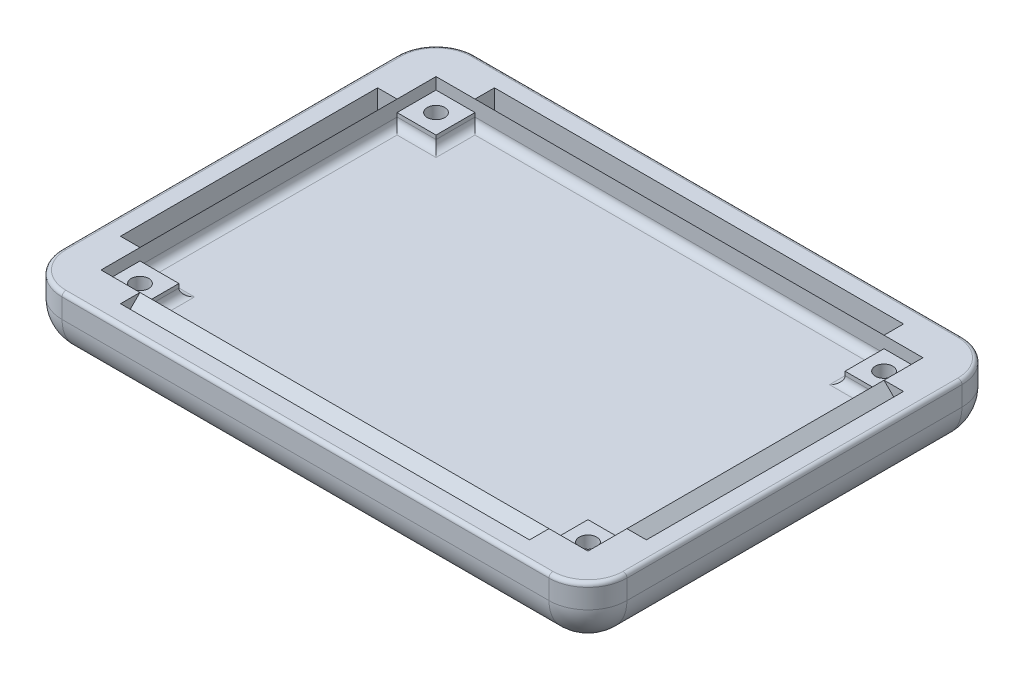
SolidWorks part; units mm, degrees
ref_plane "Front Plane" through (0, 0, 0) normal (0, 0, 1) x (1, 0, 0)
ref_plane "Top Plane" through (0, 0, 0) normal (0, 1, 0) x (1, 0, 0)
ref_plane "Right Plane" through (0, 0, 0) normal (1, 0, 0) x (0, 0, -1)
sketch "Sketch1" plane through (0, 0, 0) normal (0, 1, 0) x (1, 0, 0)
  line L0 (62.5, -43) -> (62.5, 43)
  line L1 (72.5, -53) -> (-72.5, -53)
  line L2 (72.5, -53) -> (72.5, 53)
  line L3 (72.5, 53) -> (-72.5, 53)
  line L4 (-72.5, -53) -> (-72.5, 53)
  line L5 (0, 53) -> (0, -53) construction
  line L6 (72.5, 0) -> (-72.5, 0) construction
  line L7 (62.5, 43) -> (-62.5, 43)
  line L8 (-62.5, -43) -> (-62.5, 43)
  line L9 (62.5, -43) -> (-62.5, -43)
  point P0 (0, 0)
  point P12 (0, 0)
  point P13 (0, 0)
  dimension "D1" = 145
  dimension "D2" = 106
  dimension "D3" = 10
extrude "Boss-Extrude1" add sketch "Sketch1" along normal blind 16 contours L9 L0 L7 L8 | L0 L9 L8 L7 | L4 L1 L2 L3 region at (0, 0, 0) region at (0, 0, 51.2039)
extrude "Cut-Extrude1" cut sketch "Sketch1<4>" against normal offset from surface (6 mm away) 10 from surface contours L8 L7 L0 L9 up to face at (0, 0, 0) starting at face at (0, 16, 0)
sketch "Sketch1<4>" plane through (0, 0, 0) normal (0, 1, 0) x (1, 0, 0) same geometry as "Sketch1"
sketch "Sketch3" plane through (0, 0, 0) normal (1, 0, 0) x (0, 0, -1)
  line L0 (-53, 16) -> (53, 16) construction
  line L2 (-48, 16) -> (-43, 16)
  line L3 (-53, 16) -> (-53, 0) construction
  line L4 (-48, 16) -> (-48, 11)
  line L5 (-48, 11) -> (-43, 16)
  point P6 (-46.4757, 16)
  point P7 (0, 0)
  dimension "D1" = 5
  dimension "D2" = 5
extrude "Cut-Extrude3" cut sketch "Sketch3" against normal offset from surface 10 and the other way offset from surface 10 up to face at (-62.5, 13, 0) other way up to face at (62.5, 13, 0)
sketch "Sketch4" plane through (0, 0, 0) normal (0, 0, 1) x (1, 0, 0)
  line L0 (72.5, 16) -> (-72.5, 16) construction
  line L1 (-62.5, 16) -> (-67.5, 16)
  line L2 (-67.5, 16) -> (-67.5, 11)
  line L3 (-67.5, 11) -> (-62.5, 16)
  line L4 (-72.5, 16) -> (-72.5, 0) construction
  dimension "D1" = 5
  dimension "D2" = 5
extrude "Cut-Extrude4" cut sketch "Sketch4" against normal offset from surface 10 and the other way offset from surface 10 up to face at (0, 13, -43) other way up to face at (0, 14, 43)
mirror "Mirror1" about plane through (0, 0, 0) normal (1, 0, 0) of "Cut-Extrude4"
mirror "Mirror4" about plane through (0, 0, 0) normal (0, 0, 1) of "Cut-Extrude3"
fillet "Fillet1" radius 10 8 edges at (0, 0, 53) (72.5, 0, 0) (0, 0, -53) (-72.5, 0, 0) (-72.5, 8, -53) (72.5, 8, -53) (72.5, 8, 53) (-72.5, 8, 53)
sketch "Sketch5" plane through (0, 10, 0) normal (0, 1, 0) x (1, 0, 0)
  line L2 (-62.5, 33) -> (-67.5, 33) construction
  line L3 (-52.5, 33) -> (-62.5, 33)
  line L4 (-62.5, -43) -> (62.5, -43)
  line L5 (62.5, -43) -> (62.5, 43)
  line L6 (62.5, 43) -> (-62.5, 43)
  line L7 (-62.5, 43) -> (-62.5, -43)
  line L8 (-62.5, -43) -> (62.5, -43)
  line L9 (62.5, -43) -> (62.5, 43)
  line L12 (-52.5, 33) -> (-52.5, 43)
  line L13 (-52.5, 43) -> (-62.5, 43)
  line L14 (-62.5, 33) -> (-62.5, 43)
  line L15 (-57.5, 43) -> (-57.5, 33) construction
  line L16 (-52.5, 38) -> (-62.5, 38) construction
  line L17 (-52.5, 43) -> (-52.5, 48) construction
  line L18 (-62.5, 43) -> (-62.5, 33) construction
  point P2 (-57.5, 38)
  point P15 (0, 0)
  line M7 (62.5, 43) -> (-62.5, 43)
  line M8 (-62.5, 43) -> (-62.5, -43)
  dimension "D1" = 0
extrude "Boss-Extrude3" add sketch "Sketch5" along normal blind 3 contours L3 L12 M7 M8 region at (-57.5, 10, -38)
hole_wizard "M4 Clearance Hole1" positions "Sketch6" profile "Sketch7" hole size "M4" standard "ANSI Metric"
sketch "Sketch6" plane through (0, 13, 0) normal (0, 1, 0) x (1, 0, 0)
  point P0 (-57.5, 38)
sketch "Sketch7" plane through (-57.5, 13, -38) normal (1, 0, 0) x (0, 0, 1)
  line L0 (0, 0) -> (0, 7.25)
  line L1 (0, 7.25) -> (2.25, 5)
  line L2 (2.25, 5) -> (2.25, 0)
  line L5 (2.25, 0) -> (0, 0)
  line L10 (0, 7.25) -> (-2.25, 5) construction
  line L11 (0, -6.35) -> (0, 107.95) construction
  dimension "Hole Dia." = 4.5
  dimension "Hole Depth" = 5
  dimension "Drill Angle" = 90
mirror "Mirror5" about plane through (0, 0, 0) normal (0, 0, 1) of "M4 Clearance Hole1", "Boss-Extrude3"
mirror "Mirror6" about plane through (0, 0, 0) normal (1, 0, 0) of "Mirror5", "M4 Clearance Hole1", "Boss-Extrude3"
fillet "Fillet3" radius 2 12 edges at (52.5, 10, 38) (0, 10, 43) (-52.5, 10, 38) (-57.5, 10, 33) (-62.5, 10, 0) (-57.5, 10, -33) (-52.5, 10, -38) (0, 10, -43) (52.5, 10, -38) (57.5, 10, -33) (62.5, 10, 0) (57.5, 10, 33)
fillet "Fillet11" radius 1 8 edges at (-69.5711, 16, 50.0711) (0, 16, 53) (69.5711, 16, 50.0711) (72.5, 16, 0) (69.5711, 16, -50.0711) (0, 16, -53) (-69.5711, 16, -50.0711) (-72.5, 16, 0)
equation "\"wall_thickness\"= 5mm"
